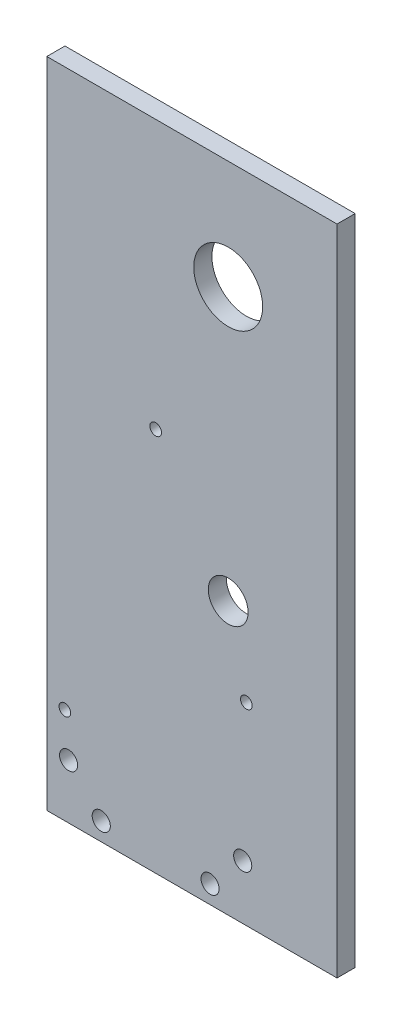
SolidWorks part; units mm, degrees
material "Thornel Mat VMA"
ref_plane "Front Plane" through (0, 0, 0) normal (0, 0, 1) x (1, 0, 0)
ref_plane "Top Plane" through (0, 0, 0) normal (0, 1, 0) x (1, 0, 0)
ref_plane "Right Plane" through (0, 0, 0) normal (1, 0, 0) x (0, 0, -1)
sketch "Sketch1" plane through (0, 0, 0) normal (0, 0, 1) x (1, 0, 0)
  line L0 (0, 103.759) -> (0, -103.759) construction
  line L1 (-30, 76) -> (50, 76)
  line L2 (-30, 76) -> (-30, 256)
  line L3 (-30, 256) -> (50, 256)
  line L4 (50, 76) -> (50, 256)
  circle A0 centre (20, 226) radius 9.5
  dimension "D1" = 150
  dimension "D5" = 19
  dimension "D2" = 20
  dimension "D3" = 180
  dimension "D4" = 80
extrude "Boss-Extrude1" add sketch "Sketch1" along normal blind 5
sketch "Sketch2" plane through (0, 0, 5) normal (0, 0, 1) x (1, 0, 0)
  line L0 (20, 226) -> (20, 151) construction
  line L1 (20, 226) -> (-17.1819, 226) construction
  circle A0 centre (20, 151) radius 5.5
  dimension "D3" = 11
  dimension "D1" = 75
  dimension "D2" = 90
extrude "Cut-Extrude1" cut sketch "Sketch2" against normal blind 30
sketch "Sketch3" plane through (0, 0, 5) normal (0, 0, 1) x (1, 0, 0)
  circle A0 centre (0, 182) radius 1.6
  circle A1 centre (25, 129.3013) radius 1.6
  circle A2 centre (-25.0329, 102.5335) radius 1.6
  circle A3 centre (-15, 81) radius 2.5
  circle A4 centre (15, 81) radius 2.5
  circle A5 centre (24, 91) radius 2.5
  circle A6 centre (-24, 91) radius 2.5
  dimension "D1" = 5
  dimension "D2" = 3.2
extrude "Cut-Extrude2" cut sketch "Sketch3" against normal blind 5
